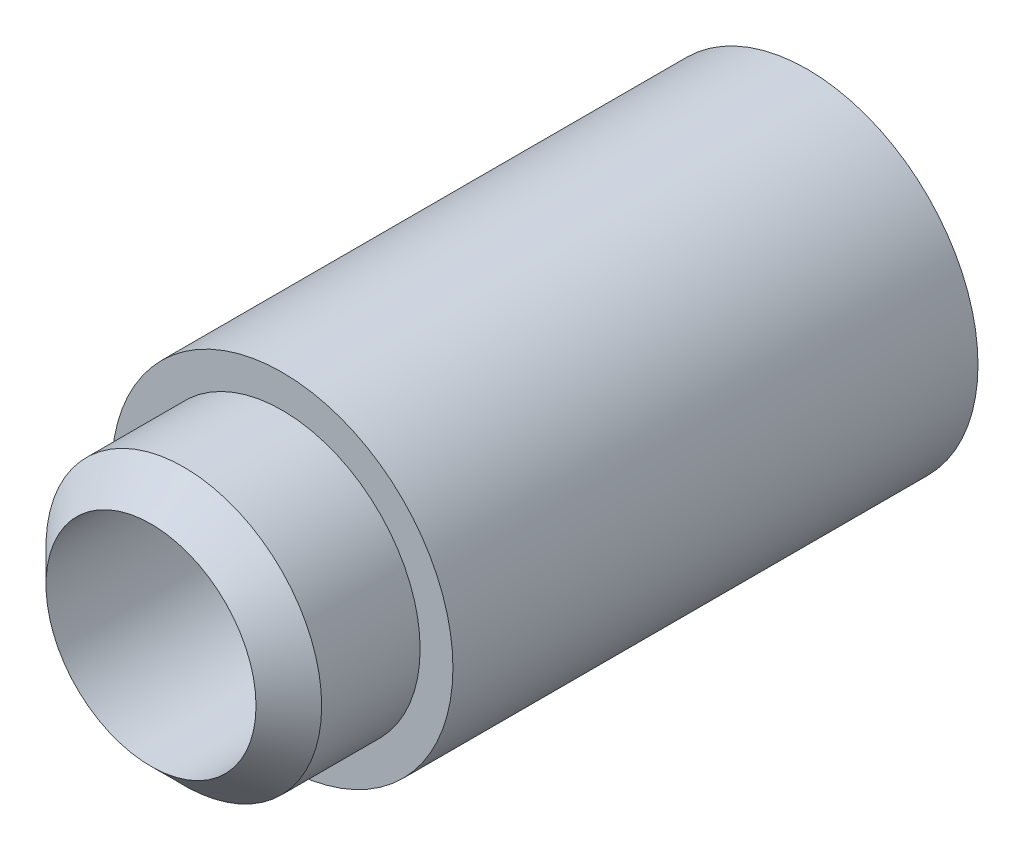
SolidWorks part; units mm, degrees
ref_plane "Front Plane" through (0, 0, 0) normal (0, 0, 1) x (1, 0, 0)
ref_plane "Top Plane" through (0, 0, 0) normal (0, 1, 0) x (1, 0, 0)
ref_plane "Right Plane" through (0, 0, 0) normal (1, 0, 0) x (0, 0, -1)
sketch "Sketch15" plane through (0, 0, 0) normal (0, 0, 1) x (1, 0, 0)
  circle A2 centre (0, 0) radius 26
  circle A3 centre (0, 0) radius 21
  dimension "D1" = 52
  dimension "D2" = 5
extrude "Boss-Extrude2" add sketch "Sketch15" along normal blind 80
sketch "Sketch18" plane through (0, 0, 80) normal (0, 0, 1) x (1, 0, 0)
  circle A1 centre (0, 0) radius 21 construction
  circle A3 centre (0, 0) radius 21
  circle A4 centre (0, 0) radius 16
  dimension "D1" = 5
extrude "Boss-Extrude5" add sketch "Sketch18" along normal blind 30 from offset 10 offset against normal yes
chamfer "Chamfer1" distance 5 angle 45 1 edges at (21, 0, 100)
